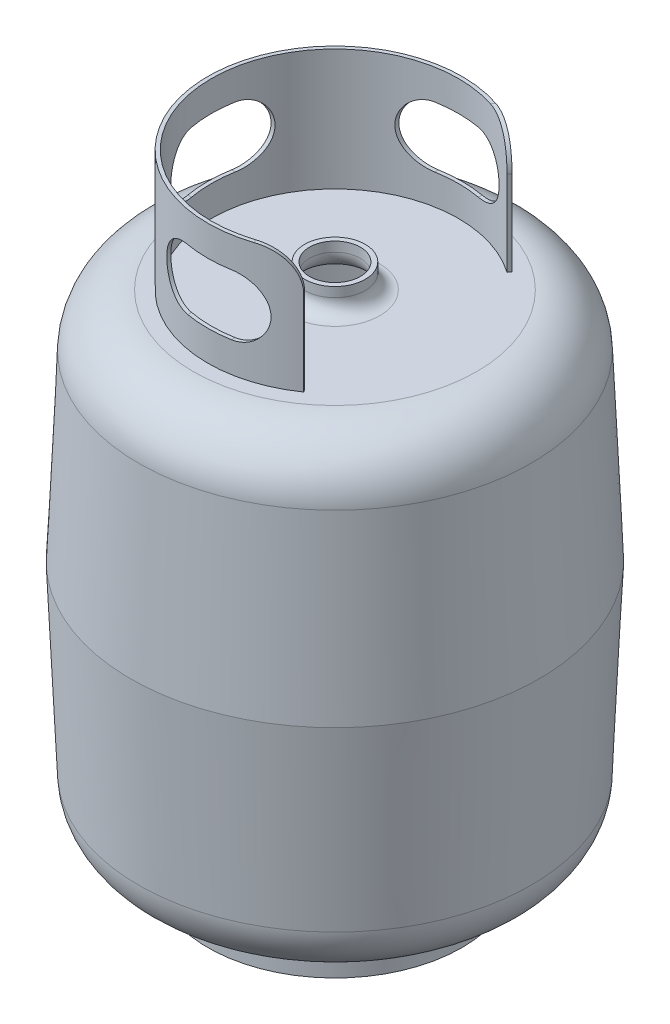
SolidWorks part; units mm, degrees
material "1060 Alloy"
ref_plane "Front Plane" through (0, 0, 0) normal (0, 0, 1) x (1, 0, 0)
ref_plane "Top Plane" through (0, 0, 0) normal (0, 1, 0) x (1, 0, 0)
ref_plane "Right Plane" through (0, 0, 0) normal (1, 0, 0) x (0, 0, -1)
sketch "Sketch1" plane through (0, 0, 0) normal (0, 0, 1) x (1, 0, 0)
  line L0 (0, 579.0191) -> (0, 0) construction
  line L1 (0, 0) -> (116.9219, 0)
  line L2 (161.879, 43.0371) -> (168.4593, 193.75)
  line L3 (168.4593, 193.75) -> (161.879, 344.4629)
  line L4 (116.9219, 387.5) -> (37, 387.5)
  line L5 (0, 407.5) -> (25, 407.5)
  line L6 (25, 407.5) -> (25, 399.5)
  line L7 (0, 403.5) -> (21, 403.5)
  line L8 (21, 403.5) -> (21, 399.5)
  line L9 (116.9219, 383.5) -> (37, 383.5)
  line L10 (164.4555, 193.75) -> (157.8828, 344.2884)
  line L11 (157.8828, 43.2116) -> (164.4555, 193.75)
  line L12 (0, 4) -> (116.9219, 4)
  line L13 (0, 407.5) -> (0, 403.5)
  line L14 (0, 4) -> (0, 0)
  arc A0 (116.9219, 0) -> (161.879, 43.0371) centre (116.9219, 45) ccw
  arc A1 (161.879, 344.4629) -> (116.9219, 387.5) centre (116.9219, 342.5) ccw
  arc A2 (25, 399.5) -> (37, 387.5) centre (37, 399.5) ccw
  arc A3 (21, 399.5) -> (37, 383.5) centre (37, 399.5) ccw
  arc A4 (157.8828, 344.2884) -> (116.9219, 383.5) centre (116.9219, 342.5) ccw
  arc A5 (116.9219, 4) -> (157.8828, 43.2116) centre (116.9219, 45) ccw
  point P7 (160, 0)
  point P13 (160, 387.5)
  point P18 (25, 387.5)
  dimension "D3" = 45
  dimension "D8" = 45
  dimension "D11" = 12
  dimension "D1" = 579.0191
  dimension "D2" = 160
  dimension "D4" = 387.5
  dimension "D5" = 92.5
  dimension "D6" = 92.5
  dimension "D7" = 193.75
  dimension "D9" = 25
  dimension "D10" = 20
  dimension "D12" = 4
revolve "Revolve1" add sketch "Sketch1" angle 360 about L0
sketch "Sketch3" plane through (0, 407.5, 0) normal (0, 1, 0) x (1, 0, 0)
  circle A0 centre (0, 0) radius 21
  dimension "D1" = 42
extrude "Cut-Extrude1" cut sketch "Sketch3" against normal blind 30
sketch "Sketch5" plane through (0, 0, 0) normal (0, -1, 0) x (1, 0, 0)
  circle A0 centre (0, 0) radius 104.9219
  circle A1 centre (0, 0) radius 116.9219
  circle A2 centre (0, 0) radius 116.9219 construction
  circle A3 centre (0, 0) radius 101.9219
  dimension "D2" = 12
  dimension "D1" = 0
  dimension "D3" = 3
extrude "Boss-Extrude1" add sketch "Sketch5" along normal blind 30
sketch "Sketch6" plane through (0, 387.5, 0) normal (0, 1, 0) x (1, 0, 0)
  line L0 (0, 0) -> (215.5386, 0) construction
  line L1 (0, 0) -> (128.2377, 183.1424) construction
  line L2 (0, 0) -> (129.1217, -184.405) construction
  line L3 (60.1807, 85.947) -> (58.46, 83.4895)
  line L4 (58.46, -83.4895) -> (60.1807, -85.947)
  arc A0 (60.1807, 85.947) -> (60.1807, -85.947) centre (0, 0) ccw
  circle A1 centre (0, 0) radius 116.9219
  circle A2 centre (0, 0) radius 116.9219 construction
  arc A3 (58.46, 83.4895) -> (58.46, -83.4895) centre (0, 0) ccw
  dimension "D2" = 12
  dimension "D3" = 55
  dimension "D4" = 55
  dimension "D1" = 0
  dimension "D5" = 3
extrude "Boss-Extrude3" add sketch "Sketch6" along normal blind 100
fillet "Fillet2" radius 30 2 edges at (59.3203, 487.5, 84.7182) (59.3203, 487.5, -84.7182)
sketch "Sketch7" plane through (0, 0, 0) normal (0, 0, 1) x (1, 0, 0)
  line L0 (0, -30) -> (0, 503.9213) construction
  line L1 (-104.9219, -30) -> (104.9219, -30) construction
  line L2 (-18, 437.5) -> (18, 437.5) construction
  line L3 (-18, 462.5) -> (18, 462.5)
  line L4 (-18, 412.5) -> (18, 412.5)
  arc A0 (-18, 462.5) -> (-18, 412.5) centre (-18, 437.5) ccw
  arc A1 (18, 412.5) -> (18, 462.5) centre (18, 437.5) ccw
  point P7 (0, 437.5)
  point P12 (0, 0)
  dimension "D2" = 25
  dimension "D1" = 50
  dimension "D3" = 36
extrude "Cut-Extrude2" cut sketch "Sketch7" against normal mid plane 290
sketch "Sketch8" plane through (0, 0, 0) normal (1, 0, 0) x (0, 0, -1)
  line L0 (0, -30) -> (0, 487.5) construction
  line L1 (-104.9219, -30) -> (104.9219, -30) construction
  line L2 (104.9219, 487.5) -> (-104.9219, 487.5) construction
  line L3 (18, 437.5) -> (-18, 437.5) construction
  line L4 (18, 412.5) -> (-18, 412.5)
  line L5 (18, 462.5) -> (-18, 462.5)
  arc A0 (18, 412.5) -> (18, 462.5) centre (18, 437.5) ccw
  arc A1 (-18, 462.5) -> (-18, 412.5) centre (-18, 437.5) ccw
  point P8 (0, 437.5)
  point P13 (0, 0)
  dimension "D2" = 25
  dimension "D1" = 50
  dimension "D3" = 36
extrude "Cut-Extrude3" cut sketch "Sketch8" against normal mid plane 290
equation "\"A\"= 325mm"
equation "\"B\"= 387.50mm"
